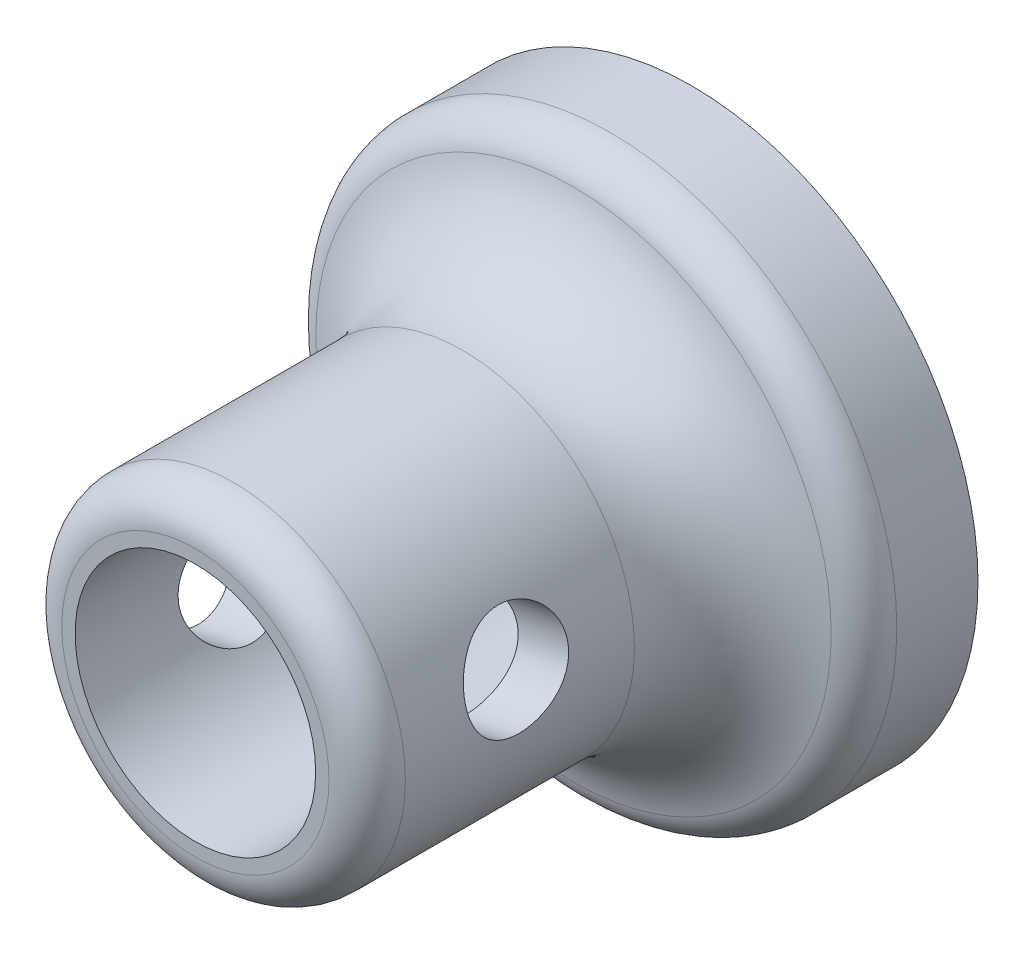
SolidWorks part; units mm, degrees
ref_plane "前视基准面" through (0, 0, 0) normal (0, 0, 1) x (1, 0, 0)
ref_plane "上视基准面" through (0, 0, 0) normal (0, 1, 0) x (1, 0, 0)
ref_plane "右视基准面" through (0, 0, 0) normal (1, 0, 0) x (0, 0, -1)
other "Configuration Table"
sketch "草图6" plane through (0, 0, 0) normal (0, 0, 1) x (1, 0, 0)
  circle A0 centre (18.1431, 29.9368) radius 7.5
  dimension "D1" = 15
extrude "凸台-拉伸1" add sketch "草图6" along normal blind 3
sketch "草图7" plane through (0, 0, 3) normal (0, 0, 1) x (1, 0, 0)
  circle A0 centre (18.1431, 29.9368) radius 4.5
  circle A1 centre (18.1431, 29.9368) radius 3.15
  dimension "D1" = 9
  dimension "D2" = 6.3
extrude "凸台-拉伸2" add sketch "草图7" along normal blind 10
fillet "圆角1" radius 3 1 edges at (22.6431, 29.9368, 3)
sketch "草图9" plane through (0, 0, 3) normal (0, 0, 1) x (1, 0, 0)
  circle A1 centre (18.1431, 29.9368) radius 1.65
  dimension "D1" = 3.3
extrude "切除-拉伸1" cut sketch "草图9" against normal up to surface (3 mm away) up to face at (25.6431, 29.9368, 0)
fillet "圆角2" radius 1 2 edges at (25.6431, 29.9368, 3) (22.6431, 29.9368, 13)
ref_plane "基准面1" through (18.9215, 3.9057, 0) normal (-0.9794, -0.2022, 0) x (0, 0, 1)
sketch "草图10" plane through (18.9215, 3.9057, 0) normal (-0.9794, -0.2022, 0) x (0, 0, 1)
  line L0 (9, 25.6511) -> (13, 25.6511) construction
  line L1 (13, 22.1511) -> (13, 29.1511) construction
  circle A0 centre (9, 25.6511) radius 1.35
  dimension "D2" = 2.7
  dimension "D1" = 4
extrude "切除-拉伸2" cut sketch "草图10" against normal through all
